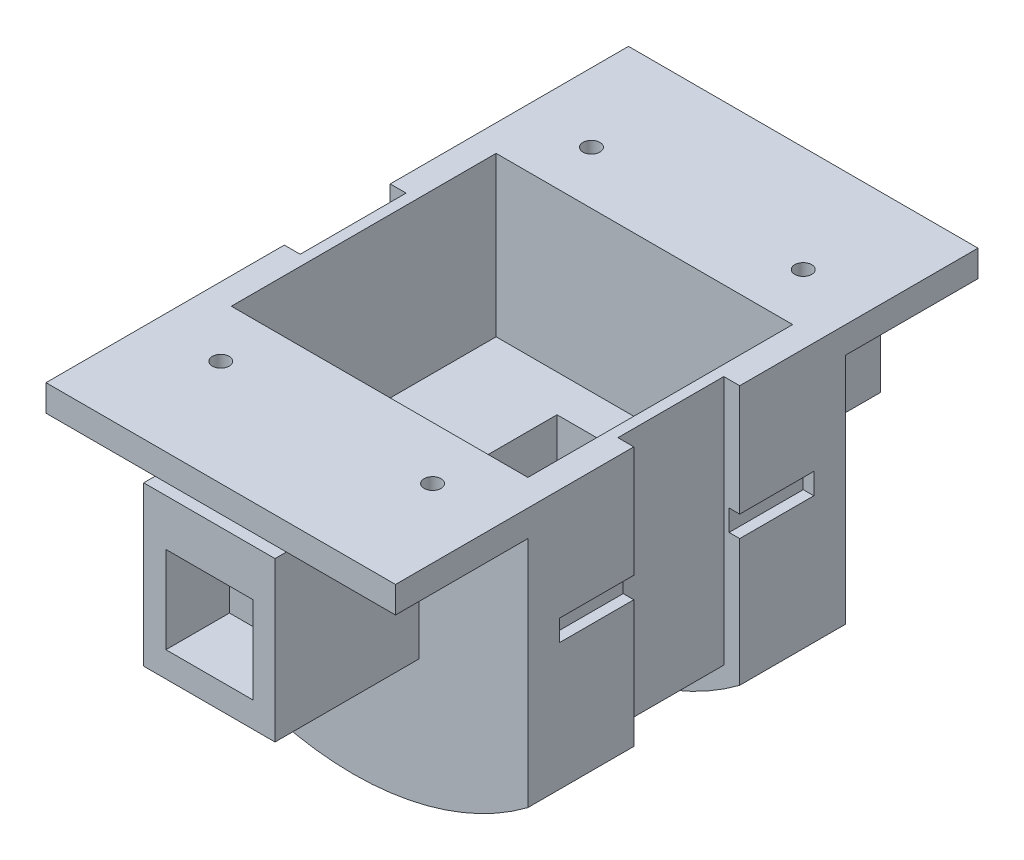
SolidWorks part; units mm, degrees
ref_plane "Front Plane" through (0, 0, 0) normal (0, 0, 1) x (1, 0, 0)
ref_plane "Top Plane" through (0, 0, 0) normal (0, 1, 0) x (1, 0, 0)
ref_plane "Right Plane" through (0, 0, 0) normal (1, 0, 0) x (0, 0, -1)
sketch "Sketch1" plane through (0, 0, 0) normal (0, 0, 1) x (1, 0, 0)
  line L0 (0, 0) -> (0, -42) construction
  line L1 (0, 0) -> (55, 0)
  line L2 (55, 0) -> (-55, 0)
  arc A0 (-55, 0) -> (55, 0) centre (0, 0) ccw
  dimension "D2" = 55
  dimension "D1" = 42
extrude "Boss-Extrude1" add sketch "Sketch1" along normal blind 30 and the other way blind 30 contours L2 A0 L1 region at (0, -23.3427, 0)
sketch "Sketch2" plane through (0, 0, 0) normal (0, 0, 1) x (1, 0, 0)
  line L1 (0, 0) -> (-9.5, 0)
  line L3 (2.8861, -52) -> (-9.5, -52)
  line L4 (-9.5, 0) -> (-9.5, -52)
  line L5 (0, 0) -> (9.5, 0)
  line L7 (2.8861, -52) -> (9.5, -52)
  line L8 (9.5, 0) -> (9.5, -52)
  circle A0 centre (0, 0) radius 42
  dimension "D1" = 84
  dimension "D2" = 9.5
  dimension "D3" = 9.5
  dimension "D4" = 52
extrude "Cut-Extrude1" cut sketch "Sketch2" against normal blind 18 and the other way blind 18 contours L4 A0 L8 L5 L1 | A0 L4 L3 | A0 L3 L7 L8 region at (0, -20.8208, 0) region at (0, -46.8145, 0)
sketch "Sketch3" plane through (0, 0, 30) normal (0, 0, 1) x (1, 0, 0)
  line L0 (0, 0) -> (0, -28.5435) construction
  line L1 (-54.8544, -4) -> (-33, -4)
  line L2 (-54.8544, -4) -> (-54.8544, -49)
  line L3 (-54.8544, -49) -> (-33, -49)
  line L4 (-33, -4) -> (-33, -49)
  line L5 (55, 0) -> (-55, 0) construction
  line L6 (33, -4) -> (33, -49)
  line L7 (54.8544, -49) -> (33, -49)
  line L8 (54.8544, -4) -> (54.8544, -49)
  line L9 (54.8544, -4) -> (33, -4)
  arc A0 (-55, 0) -> (55, 0) centre (0, 0) ccw construction
  dimension "D1" = 4
  dimension "D2" = 33
  dimension "D3" = 45
extrude "Cut-Extrude2" cut sketch "Sketch3" against normal through all
sketch "Sketch4" plane through (0, 0, 0) normal (0, 1, 0) x (1, 0, 0)
  line L0 (55, 30) -> (-55, 30) construction
  line L1 (55, 30) -> (55, -30) construction
  line L2 (0, 0) -> (0, 55.9923) construction
  line L3 (0, 0) -> (36.0907, 0) construction
  circle A0 centre (45, 20) radius 1.6
  circle A1 centre (45, -20) radius 1.6
  circle A2 centre (-45, -20) radius 1.6
  circle A3 centre (-45, 20) radius 1.6
  dimension "D1" = 3.2
  dimension "D2" = 10
  dimension "D3" = 10
extrude "Cut-Extrude3" cut sketch "Sketch4" against normal through all
sketch "Sketch6" plane through (33, 0, 0) normal (1, 0, 0) x (0, 0, -1)
  line L0 (-30, -4) -> (-30, -44) construction
  line L1 (-24, -16) -> (24, -16)
  line L2 (-24, -16) -> (-24, -20)
  line L3 (-24, -20) -> (24, -20)
  line L4 (24, -16) -> (24, -20)
  line L5 (30, -4) -> (30, -44) construction
  line L6 (30, -4) -> (-30, -4) construction
  dimension "D1" = 6
  dimension "D2" = 6
  dimension "D3" = 12
  dimension "D4" = 4
extrude "Cut-Extrude5" cut sketch "Sketch6" against normal blind 2
sketch "Sketch9" plane through (0, 0, 0) normal (0, 1, 0) x (1, 0, 0)
  line L5 (-55, 30) -> (-33, 30)
  line L6 (-55, 30) -> (-55, -30)
  line L7 (-55, -30) -> (-33, -30)
  line L8 (-33, 30) -> (-33, -30)
  line L9 (55, 30) -> (33, 30)
  line L10 (55, 30) -> (55, -30)
  line L11 (55, -30) -> (33, -30)
  line L12 (33, 30) -> (33, -30)
extrude "Cut-Extrude7" cut sketch "Sketch9" against normal through all
sketch "Sketch10" plane through (0, 0, 0) normal (0, 1, 0) x (1, 0, 0)
  line L1 (-33, 30) -> (33, 30)
  line L2 (-33, 30) -> (-33, -30)
  line L3 (-33, -30) -> (33, -30)
  line L4 (33, 30) -> (33, -30)
  line L5 (33, -30) -> (-33, -30)
  line L6 (33, -30) -> (33, -55)
  line L7 (33, -55) -> (-33, -55)
  line L8 (-33, -30) -> (-33, -55)
  line L9 (-33, 30) -> (33, 30)
  line L10 (-33, 30) -> (-33, 55)
  line L11 (-33, 55) -> (33, 55)
  line L12 (33, 30) -> (33, 55)
  line L13 (-9.5, 18) -> (9.5, 18)
  line L14 (-9.5, 18) -> (-9.5, -18)
  line L15 (-9.5, -18) -> (9.5, -18)
  line L16 (9.5, 18) -> (9.5, -18)
  line M3 (-33, 30) -> (-33, -30)
  line M4 (-33, -30) -> (33, -30)
  line M5 (33, -30) -> (33, 30)
  line M6 (33, 30) -> (-33, 30)
  line M7 (9.5, -18) -> (-9.5, -18)
  line M8 (-9.5, -18) -> (-9.5, 18)
  line M9 (-9.5, 18) -> (9.5, 18)
  line M10 (9.5, 18) -> (9.5, -18)
  dimension "D1" = 25
  dimension "D2" = 25
extrude "Boss-Extrude2" add sketch "Sketch10" along normal blind 5 contours L12 L11 L10 M6 | M6 M3 M4 M5 M10 M7 M8 M9 | L8 L7 L6 M4 region at (0, 0, -42.5) region at (0, 0, -29.108) region at (0, 0, 42.5)
sketch "Sketch11" plane through (0, 5, 0) normal (0, 1, 0) x (1, 0, 0)
  line L0 (0, 0) -> (-22.9202, 0) construction
  line L1 (-22.9202, 0) -> (0, 0) construction
  circle A0 centre (-20, 35) radius 1.6
  circle A1 centre (20, 35) radius 1.6
  circle A2 centre (-20, -35) radius 1.6
  circle A3 centre (20, -35) radius 1.6
  dimension "D1" = 3.2
  dimension "D2" = 35
  dimension "D3" = 20
  dimension "D5" = 40
  dimension "D4" = 2
extrude "Cut-Extrude8" cut sketch "Sketch11" against normal through all
sketch "Sketch13" plane through (0, 0, -30) normal (0, 0, -1) x (-1, 0, 0)
  line L0 (33, 0) -> (-33, 0) construction
  line L11 (-18.4, 0) -> (-18.4, 5) construction
  line L12 (-12.4, 0) -> (12.4, 0)
  line L13 (-12.4, 0) -> (-12.4, -30)
  line L14 (-12.4, -30) -> (12.4, -30)
  line L15 (12.4, 0) -> (12.4, -30)
  line L16 (18.4, 5) -> (18.4, 0) construction
  point P0 (0, -17)
  dimension "D5" = 6
  dimension "D6" = 30
  dimension "D7" = 6
extrude "Boss-Extrude3" add sketch "Sketch13" along normal blind 27.15
sketch "Sketch14" plane through (0, 0, -57.15) normal (0, 0, -1) x (-1, 0, 0)
  line L0 (33, -44) -> (33, 0) construction
  line L5 (33, 0) -> (12.4, 0) construction
  line L6 (0, -17) -> (0, 0) construction
  line L7 (-8, -9) -> (8, -9)
  line L8 (-8, -9) -> (-8, -25)
  line L9 (-8, -25) -> (8, -25)
  line L10 (8, -9) -> (8, -25)
  line L11 (-8, -9) -> (8, -25) construction
  line L12 (-8, -25) -> (8, -9) construction
  line L14 (-8.2, -8.8) -> (8.2, -8.8)
  line L15 (-8.2, -8.8) -> (-8.2, -25.2)
  line L16 (-8.2, -25.2) -> (8.2, -25.2)
  line L17 (8.2, -8.8) -> (8.2, -25.2)
  line L18 (-8.2, -8.8) -> (8.2, -25.2) construction
  line L19 (-8.2, -25.2) -> (8.2, -8.8) construction
  point P4 (0, -17)
  dimension "D1" = 16
  dimension "D2" = 9
  dimension "D3" = 16
  dimension "D4" = 25
  dimension "D5" = 17
  dimension "D6" = 0.2
  dimension "D7" = 0.2
extrude "Cut-Extrude9" cut sketch "Sketch14" against normal blind 12 contours L10 L7 L8 L9 | L17 L14 L15 L16 L7 L10 L9 L8 region at (0, -17, -57.15) region at (0, -8.8232, -57.15)
ref_plane "Plane1" through (0, 0, 0) normal (0, 0, -1) x (-1, 0, 0)
mirror "Mirror2" about plane through (0, 0, 0) normal (0, 0, -1) of "Boss-Extrude3"
mirror "Mirror3" about plane through (0, 0, 0) normal (0, 0, -1) of "Cut-Extrude9"
sketch "Sketch15" plane through (0, 5, 0) normal (0, 1, 0) x (1, 0, 0)
  line L0 (-12.4, 30) -> (-33, 30) construction
  line L1 (-28, 25) -> (28, 25)
  line L2 (-28, 25) -> (-28, -25)
  line L3 (-28, -25) -> (28, -25)
  line L4 (28, 25) -> (28, -25)
  line L5 (-12.4, -30) -> (-33, -30) construction
  line L6 (-33, -55) -> (-33, 55) construction
  line L7 (33, -55) -> (33, 55) construction
  dimension "D1" = 5
  dimension "D2" = 5
  dimension "D3" = 5
  dimension "D4" = 5
extrude "Cut-Extrude10" cut sketch "Sketch15" against normal blind 30
sketch "Sketch16" plane through (0, -52, 0) normal (0, 1, 0) x (1, 0, 0)
  line L0 (9.5, 18) -> (9.5, -18) construction
  line L1 (-9.5, 10) -> (9.5, 10)
  line L2 (-9.5, 10) -> (-9.5, -10)
  line L3 (-9.5, -10) -> (9.5, -10)
  line L4 (9.5, 10) -> (9.5, -10)
  line L5 (-9.5, 10) -> (9.5, -10) construction
  line L6 (-9.5, -10) -> (9.5, 10) construction
  point P0 (0, 0)
  dimension "D1" = 10
extrude "Cut-Extrude11" cut sketch "Sketch16" against normal blind 45
sketch "Sketch18" plane through (0, 0, 0) normal (0, 0, -1) x (-1, 0, 0)
  line L0 (9.5, -49.1733) -> (30, -42.1946)
  line L1 (9.5, -54.1733) -> (29.6775, -54.1733)
  line L2 (9.5, -54.1733) -> (9.5, -49.1733)
  line L5 (33, -44) -> (33, 0) construction
  line L6 (33, -41.1733) -> (33, -54.1733)
  line L7 (33, -54.1733) -> (29.6775, -54.1733)
  line L8 (33, 5) -> (-33, 5) construction
  line L10 (33, -41.1733) -> (33, 5)
  line L11 (33, 5) -> (30, 5)
  line L12 (30, -41.1733) -> (30, 5)
  line L13 (30, -41.1733) -> (30, -42.1946)
  line L14 (0, 0) -> (0, -55) construction
  line L15 (-30, -41.1733) -> (-30, -42.1946)
  line L16 (-30, -41.1733) -> (-30, 5)
  line L17 (-33, 5) -> (-30, 5)
  line L18 (-33, -41.1733) -> (-33, 5)
  line L19 (-33, -54.1733) -> (-29.6775, -54.1733)
  line L20 (-33, -41.1733) -> (-33, -54.1733)
  line L21 (-9.5, -54.1733) -> (-9.5, -49.1733)
  line L22 (-9.5, -54.1733) -> (-29.6775, -54.1733)
  line L23 (-9.5, -49.1733) -> (-30, -42.1946)
  arc A0 (-33, -44) -> (33, -44) centre (0, 0) ccw construction
  dimension "D1" = 13
  dimension "D2" = 3
extrude "Cut-Extrude19" cut sketch "Sketch18" against normal blind 10 and the other way blind 10
